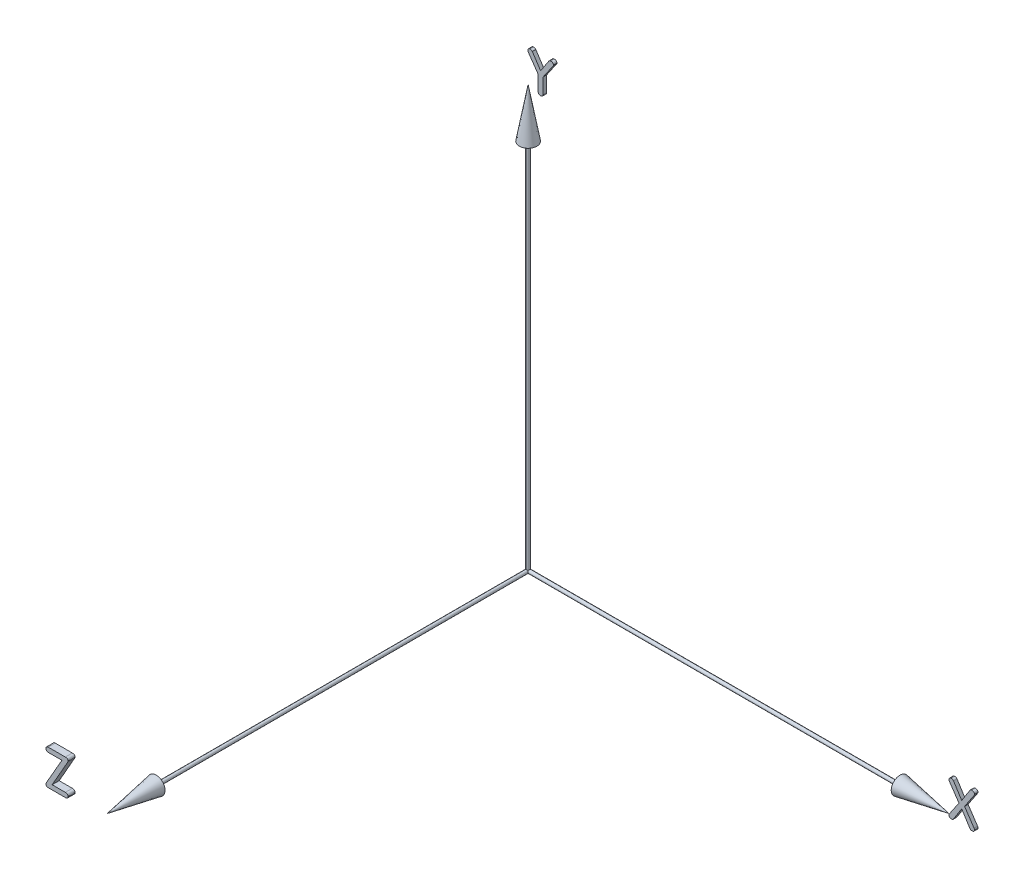
SolidWorks part; units mm, degrees
note: '?' marks a value the reader was unsure of.
ref_plane "Plan de face" through (0, 0, 0) normal (0, 0, 1) x (1, 0, 0)
ref_plane "Plan de dessus" through (0, 0, 0) normal (0, 1, 0) x (1, 0, 0)
ref_plane "Plan de droite" through (0, 0, 0) normal (1, 0, 0) x (0, 0, -1)
sketch "Esquisse1" plane through (0, 0, 0) normal (0, 0, 1) x (1, 0, 0)
  line L0 (0, 0.25) -> (53, 0.25)
  line L1 (53, 0.25) -> (53, 1.25)
  line L2 (53, 1.25) -> (60, 0)
  line L3 (-16.1702, 0) -> (81.7375, 0) construction
  line L4 (0, 0.25) -> (0, 0)
  line L5 (0, 0) -> (60, 0)
  dimension "D1" = 0.25
  dimension "D2" = 1.25
  dimension "D3" = 7
  dimension "D4" = 60
revolve "Révolution1" add sketch "Esquisse1" angle 360 about L3
ref_axis "Axe1" through (0, 0, -1.1) along (0, 0, 1)?
pattern_circular "Répétition circulaire1" count 2 every 90 about axis through (0, 0, -1.1) along (0, 0, 1) of "Révolution1"
ref_axis "Axe2" through (53, 0, 0) along (-1, 0, 0)?
pattern_circular "Répétition circulaire2" count 2 over 360 about axis through (53, 0, 0) along (-1, 0, 0) of "Répétition circulaire1"
sketch "Esquisse2" plane through (0, 0, 0) normal (0, 0, 1) x (1, 0, 0)
  text T0 "X" font "ISOCPEUR" height 5
  text T1 "Y" font "ISOCPEUR" height 5
extrude "Extrusion1" add sketch "Esquisse2" along normal blind 0.5
ref_plane "Plan1" through (0, 0, 60) normal (0, 0, 1) x (1, 0, 0)
sketch "Esquisse3" plane through (0, 0, 60) normal (0, 0, 1) x (1, 0, 0)
  text T0 "Z" font "ISOCPEUR" height 5
extrude "Boss.-Extru.1" add sketch "Esquisse3" along normal blind 1 separate body
